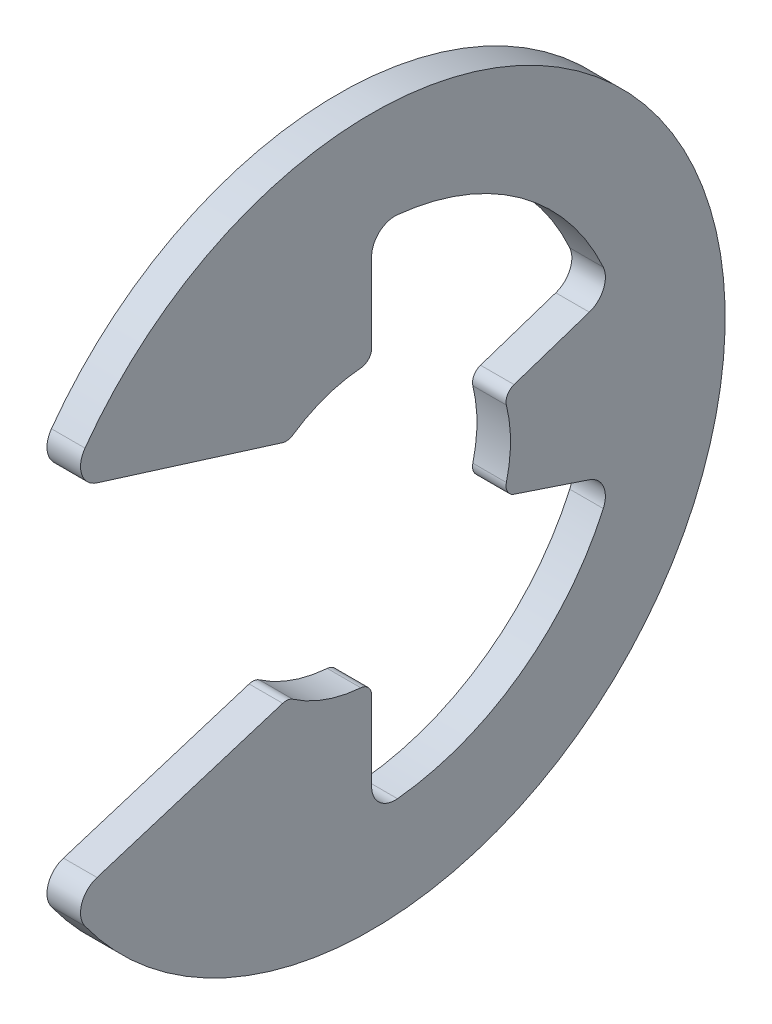
SolidWorks part; units mm, degrees
ref_plane "Front" through (0, 0, 0) normal (0, 0, 1) x (1, 0, 0)
ref_plane "Top" through (0, 0, 0) normal (0, 1, 0) x (1, 0, 0)
ref_plane "Right" through (0, 0, 0) normal (1, 0, 0) x (0, 0, -1)
sketch "Sketch1" plane through (0, 0, 0) normal (1, 0, 0) x (0, 0, -1)
  line L0 (-5.7594, -3.4095) -> (-1.5773, -2.1031)
  line L1 (-5.7594, 3.4095) -> (-1.5773, 2.1031)
  line L2 (0, -2.6289) -> (0, -4.8113)
  line L3 (0, 2.6289) -> (0, 4.8113)
  line L4 (2.494, -0.8313) -> (4.5644, -1.5215)
  line L5 (2.494, 0.8313) -> (4.5644, 1.5215)
  line L6 (0, 0) -> (-2.6289, 0) construction
  line L7 (2.494, 0.8313) -> (2.494, -0.8313) construction
  line L8 (0, -2.6289) -> (-1.5773, -2.1031) construction
  line L9 (0, 6.6929) -> (0, -6.6929) construction
  circle A2 centre (0, 0) radius 2.6289 construction
  arc A3 (-5.7594, -3.4095) -> (-5.7594, 3.4095) centre (0, 0) ccw
  arc A4 (-1.5773, -2.1031) -> (0, -2.6289) centre (0, 0) ccw
  arc A5 (-1.5773, 2.1031) -> (0, 2.6289) centre (0, 0) cw
  arc A6 (2.494, 0.8313) -> (2.494, -0.8313) centre (0, 0) cw
  arc A7 (0, -4.8113) -> (4.5644, -1.5215) centre (0, 0) ccw
  arc A8 (4.5644, 1.5215) -> (0, 4.8113) centre (0, 0) ccw
  point P8 (0, 2.6289)
  point P12 (0, 6.6929)
  dimension "Free Diameter" = 5.2578
  dimension "D1" = 4.8113
  dimension "Ring OD" = 13.3858
  dimension "D2" = 3.0743
  dimension "D10" = 4.2062
sketch "Sketch4" plane through (0, 0, 0) normal (0, 0, 1) x (1, 0, 0)
  line L0 (-0.3175, 6.6929) -> (0.3175, 6.6929) construction
  point P3 (0, 6.6929)
  dimension "Ring Thickness" = 0.635
sketch "Sketch3" plane through (0, 0, 0) normal (1, 0, 0) x (0, 0, -1)
  line L6 (2.494, -0.8313) -> (4.5644, -1.5215)
  line L7 (0, -4.8113) -> (0, -2.6289)
  line L8 (-1.5773, -2.1031) -> (-5.7594, -3.4095)
  line L9 (-5.7594, 3.4095) -> (-1.5773, 2.1031)
  line L10 (0, 2.6289) -> (0, 4.8113)
  line L11 (4.5644, 1.5215) -> (2.494, 0.8313)
  line L12 (2.494, -0.8313) -> (4.5644, -1.5215)
  line L13 (0, -4.8113) -> (0, -2.6289)
  line L14 (-1.5773, -2.1031) -> (-5.7594, -3.4095)
  line L15 (-5.7594, 3.4095) -> (-1.5773, 2.1031)
  line L16 (0, 2.6289) -> (0, 4.8113)
  line L17 (4.5644, 1.5215) -> (2.494, 0.8313)
  arc A6 (0, -4.8113) -> (4.5644, -1.5215) centre (0, 0) ccw
  arc A7 (-1.5773, -2.1031) -> (0, -2.6289) centre (0, 0) ccw
  arc A8 (-5.7594, -3.4095) -> (-5.7594, 3.4095) centre (0, 0) ccw
  arc A9 (0, 2.6289) -> (-1.5773, 2.1031) centre (0, 0) ccw
  arc A10 (4.5644, 1.5215) -> (0, 4.8113) centre (0, 0) ccw
  arc A11 (2.494, -0.8313) -> (2.494, 0.8313) centre (0, 0) ccw
  arc A12 (0, -4.8113) -> (4.5644, -1.5215) centre (0, 0) ccw
  arc A13 (-1.5773, -2.1031) -> (0, -2.6289) centre (0, 0) ccw
  arc A14 (-5.7594, -3.4095) -> (-5.7594, 3.4095) centre (0, 0) ccw
  arc A15 (0, 2.6289) -> (-1.5773, 2.1031) centre (0, 0) ccw
  arc A16 (4.5644, 1.5215) -> (0, 4.8113) centre (0, 0) ccw
  arc A17 (2.494, -0.8313) -> (2.494, 0.8313) centre (0, 0) ccw
  dimension "D1" = 0
extrude "Boss-Extrude1" add sketch "Sketch3" along normal up to vertex (0.3175 mm away) and the other way up to vertex (0.3175 mm away) up to point (0.3175, 6.6929, 0) other way up to point (-0.3175, 6.6929, 0)
fillet "Fillet1" radius 0.4445 6 edges at (0, -4.8113, 0) (0, -1.5215, -4.5644) (0, 1.5215, -4.5644) (0, 4.8113, 0) (0, -3.4095, 5.7594) (0, 3.4095, 5.7594)
fillet "Fillet2" radius 0.2223 6 edges at (0, -2.6289, 0) (0, -2.1031, 1.5773) (0, 0.8313, -2.494) (0, -0.8313, -2.494) (0, 2.1031, 1.5773) (0, 2.6289, 0)
equation "\"D1@Sketch1\" =  ( \"Ring OD@Sketch1\" + \"Free Diameter@Sketch1\" )  / 3.875"
equation "\"D10@Sketch1\"=\"Free Diameter@Sketch1\" * .8"
equation "\"D1@Fillet1\"=\"Ring Thickness@Sketch4\"*.7"
equation "\"D1@Fillet2\"=\"D1@Fillet1\"/2"
